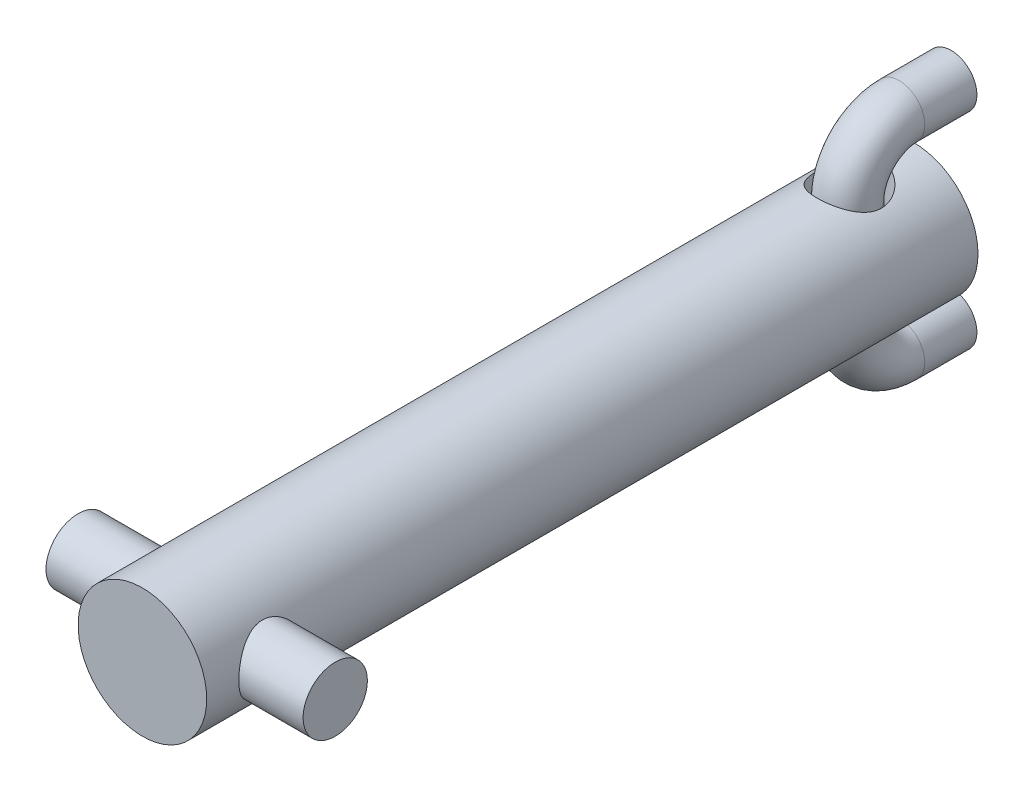
SolidWorks part; units mm, degrees
ref_plane "Front Plane" through (0, 0, 0) normal (0, 0, 1) x (1, 0, 0)
ref_plane "Top Plane" through (0, 0, 0) normal (0, 1, 0) x (1, 0, 0)
ref_plane "Right Plane" through (0, 0, 0) normal (1, 0, 0) x (0, 0, -1)
sketch "Sketch1" plane through (0, 0, 0) normal (0, 0, 1) x (1, 0, 0)
  circle A0 centre (0, 0) radius 3.175
  dimension "D1" = 6.35
extrude "Boss-Extrude1" add sketch "Sketch1" along normal blind 38.1
sketch "Sketch2" plane through (0, 0, 0) normal (0, 1, 0) x (1, 0, 0)
  circle A0 centre (0, -3.175) radius 1.5875
  dimension "D2" = 3.175
  dimension "D1" = 3.175
extrude "Cut-Extrude1" cut sketch "Sketch2" against normal mid plane 31.75
sketch "Sketch3" plane through (0, 0, 0) normal (1, 0, 0) x (0, 0, -1)
  line L0 (-38.1, 3.175) -> (-38.1, -3.175) construction
  circle A0 centre (-34.925, 0) radius 1.5875
  point P6 (-31.75, -3.175)
  dimension "D1" = 3.175
  dimension "D2" = 3.175
  dimension "D3" = 3.175
extrude "Boss-Extrude2" add sketch "Sketch3" along normal mid plane 12.7
sketch "Sketch4" plane through (0, 0, 0) normal (1, 0, 0) x (0, 0, -1)
  line L0 (-3.263, -2.6975) -> (-3.263, 2.3825)
  line L1 (-0.723, 4.9225) -> (1.8504, 4.9225)
  line L2 (-0.723, -5.2375) -> (1.8504, -5.2375)
  arc A0 (-3.263, -2.6975) -> (-0.723, -5.2375) centre (-0.723, -2.6975) ccw
  arc A1 (-0.723, 4.9225) -> (-3.263, 2.3825) centre (-0.723, 2.3825) ccw
  point P3 (-3.263, -0.1575)
  point P7 (-3.263, -5.2375)
  point P10 (-3.263, 4.9225)
  dimension "D2" = 2.54
  dimension "D1" = 10.16
sweep "Sweep1" add path "Sketch4" circular profile diameter 2.54 parameters "D3"=2.54
